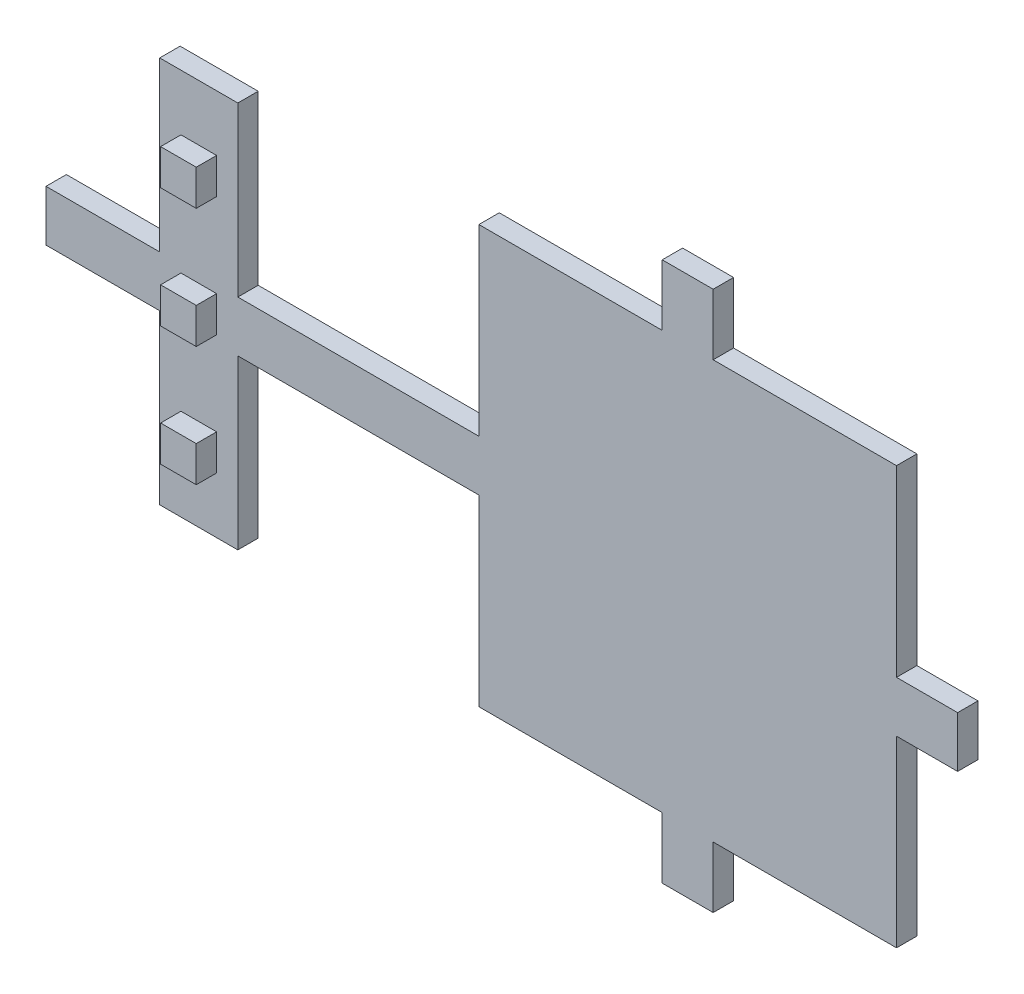
SolidWorks part; units mm, degrees
ref_plane "Front Plane" through (0, 0, 0) normal (0, 0, 1) x (1, 0, 0)
ref_plane "Top Plane" through (0, 0, 0) normal (0, 1, 0) x (1, 0, 0)
ref_plane "Right Plane" through (0, 0, 0) normal (1, 0, 0) x (0, 0, -1)
sketch "Sketch1" plane through (0, 0, 0) normal (0, 0, 1) x (1, 0, 0)
  line L1 (-41, -41) -> (41, -41)
  line L2 (-41, -41) -> (-41, 41)
  line L3 (-41, 41) -> (41, 41)
  line L4 (41, -41) -> (41, 41)
  line L5 (-41, -41) -> (41, 41) construction
  line L6 (-41, 41) -> (41, -41) construction
  point P0 (0, 0)
  dimension "D1" = 82
  dimension "D2" = 82
extrude "Boss-Extrude3" add sketch "Sketch1" along normal blind 4
ref_plane "Plane3" through (0, 0, 0) normal (1, 0, 0) x (0, 0, -1)
ref_plane "Plane4" through (0, 0, 0) normal (0, -1, 0) x (-1, 0, 0)
sketch "Sketch6" plane through (0, 41, 0) normal (0, 1, 0) x (1, 0, 0)
  line L0 (0, 0) -> (0, -4) construction
  line L1 (41, 0) -> (-41, 0) construction
  line L2 (41, -4) -> (-41, -4) construction
  line L4 (5, 0) -> (-5, 0)
  line L5 (5, 0) -> (5, -4)
  line L6 (5, -4) -> (-5, -4)
  line L7 (-5, 0) -> (-5, -4)
  line L8 (5, 0) -> (-5, -4) construction
  line L9 (5, -4) -> (-5, 0) construction
  point P6 (0, -2)
extrude "Boss-Extrude4" add sketch "Sketch6" along normal blind 12
ref_axis "Axis1" through (0, 0, 4.2) along (0, 0, -1)
pattern_circular "CirPattern1" count 3 every 90 about axis through (0, 0, 4.2) along (0, 0, -1) of "Boss-Extrude4"
sketch "Sketch8" plane through (-41, 0, 0) normal (-1, 0, 0) x (0, 0, 1)
  line L0 (0, 0) -> (4, 0) construction
  line L1 (0, 41) -> (0, -41) construction
  line L2 (4, 41) -> (4, -41) construction
  line L4 (0, 5) -> (4, 5)
  line L5 (0, 5) -> (0, -5)
  line L6 (0, -5) -> (4, -5)
  line L7 (4, 5) -> (4, -5)
  line L8 (0, 5) -> (4, -5) construction
  line L9 (0, -5) -> (4, 5) construction
  point P6 (2, 0)
extrude "Boss-Extrude5" add sketch "Sketch8" along normal blind 85
sketch "Sketch9" plane through (0, 0, 4) normal (0, 0, 1) x (1, 0, 0)
  line L0 (-126, 0) -> (-96, 0) construction
  line L1 (-126, -5) -> (-126, 5) construction
  line L3 (-92.5, 3.5) -> (-99.5, 3.5)
  line L4 (-92.5, 3.5) -> (-92.5, -3.5)
  line L5 (-92.5, -3.5) -> (-99.5, -3.5)
  line L6 (-99.5, 3.5) -> (-99.5, -3.5)
  line L7 (-92.5, 3.5) -> (-99.5, -3.5) construction
  line L8 (-92.5, -3.5) -> (-99.5, 3.5) construction
sketch "Sketch12" plane through (0, 5, 0) normal (0, 1, 0) x (1, 0, 0)
  line L0 (-126, -4) -> (-126, 0) construction
  line L2 (-126, -4) -> (-41, -4) construction
  line L3 (-103.6666, 0) -> (-88.3334, 0)
  line L4 (-103.6666, 0) -> (-103.6666, -4)
  line L5 (-103.6666, -4) -> (-88.3334, -4)
  line L6 (-88.3334, 0) -> (-88.3334, -4)
  line L7 (-103.6666, 0) -> (-88.3334, -4) construction
  line L8 (-103.6666, -4) -> (-88.3334, 0) construction
  line L9 (-96, -2) -> (-126, -2) construction
extrude "Boss-Extrude6" add sketch "Sketch12" along normal blind 33
extrude "Boss-Extrude7" add sketch "Sketch9" along normal blind 4
sketch "Sketch13" plane through (0, 0, 4) normal (0, 0, 1) x (1, 0, 0)
  line L0 (-96, 3.5) -> (-96, 23.5) construction
  line L1 (-92.5, 3.5) -> (-99.5, 3.5) construction
  line L3 (-99.5, 27) -> (-92.5, 27)
  line L4 (-99.5, 27) -> (-99.5, 20)
  line L5 (-99.5, 20) -> (-92.5, 20)
  line L6 (-92.5, 27) -> (-92.5, 20)
  line L7 (-99.5, 27) -> (-92.5, 20) construction
  line L8 (-99.5, 20) -> (-92.5, 27) construction
extrude "Boss-Extrude8" add sketch "Sketch13" along normal blind 4
mirror "Mirror2" about plane through (0, 0, 0) normal (0, -1, 0) of "Boss-Extrude6", "Boss-Extrude8"
